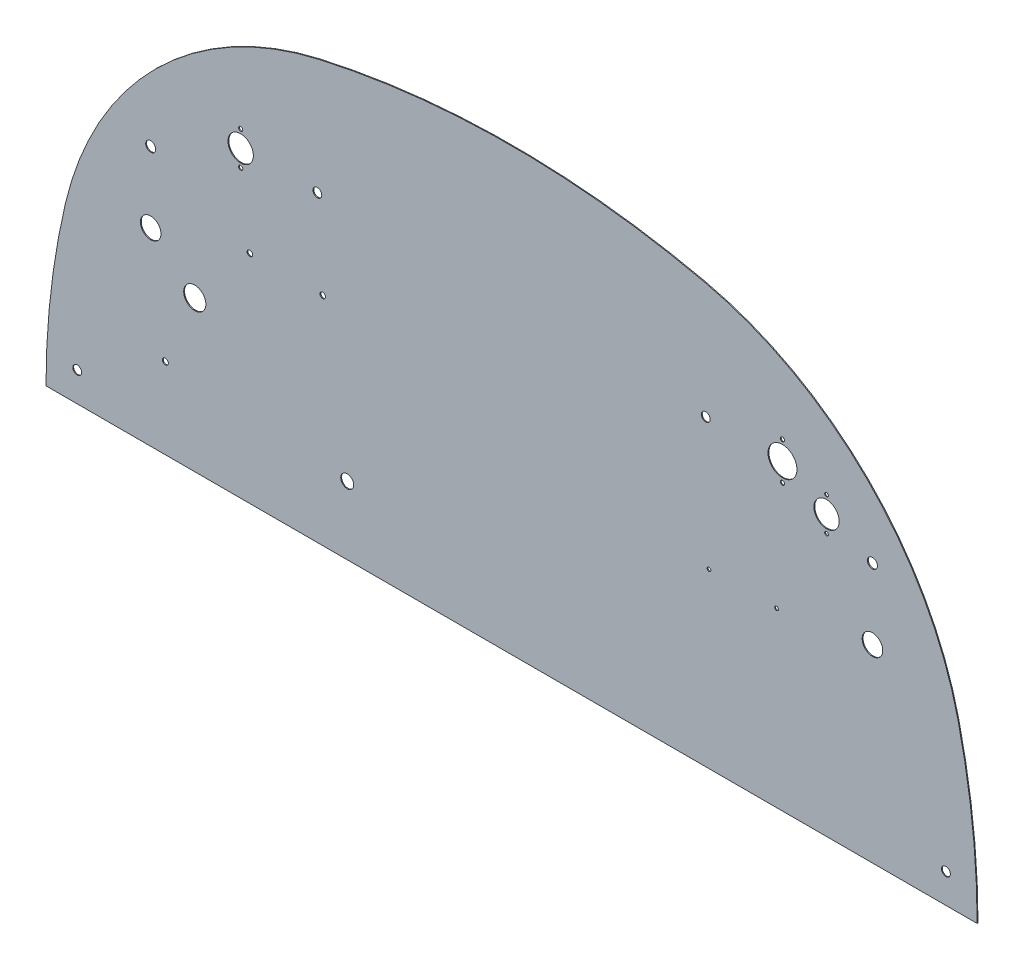
SolidWorks part; units mm, degrees
ref_plane "Front Plane" through (0, 0, 0) normal (0, 0, 1) x (1, 0, 0)
ref_plane "Top Plane" through (0, 0, 0) normal (0, 1, 0) x (1, 0, 0)
ref_plane "Right Plane" through (0, 0, 0) normal (1, 0, 0) x (0, 0, -1)
sketch "Base Sketch" plane through (0, 0, 0) normal (0, 0, 1) x (1, 0, 0)
  line L0 (0, 0) -> (750.8875, 0) construction
  line L1 (375.4437, 0) -> (375.4437, 236.5375) construction
  line L2 (543.3219, 236.5375) -> (207.5656, 236.5375) construction
  line L3 (-26.9875, -25.4) -> (777.875, -25.4)
  line L4 (375.4437, 0) -> (375.4437, -25.4) construction
  line L5 (375.4437, 236.5375) -> (375.4437, 355.6) construction
  line L6 (375.4437, 355.6) -> (-26.9875, 355.6) construction
  line L7 (-1.5875, -25.4) -> (375.4437, -25.4) construction
  line L8 (-1.5875, -25.4) -> (-1.5875, 152.4) construction
  line L9 (-1.5875, 152.4) -> (375.4437, 152.4) construction
  line L10 (375.4437, -25.4) -> (375.4437, 152.4) construction
  line L11 (23.8125, -25.4) -> (375.4437, -25.4) construction
  line L12 (23.8125, -25.4) -> (23.8125, 203.2) construction
  line L13 (23.8125, 203.2) -> (375.4437, 203.2) construction
  line L14 (375.4437, -25.4) -> (375.4437, 203.2) construction
  line L15 (49.2125, -25.4) -> (375.4437, -25.4) construction
  line L16 (49.2125, -25.4) -> (49.2125, 228.6) construction
  line L17 (49.2125, 228.6) -> (375.4437, 228.6) construction
  line L18 (375.4437, -25.4) -> (375.4437, 228.6) construction
  line L19 (74.6125, -25.4) -> (375.4437, -25.4) construction
  line L20 (74.6125, -25.4) -> (74.6125, 254) construction
  line L21 (74.6125, 254) -> (375.4437, 254) construction
  line L22 (375.4437, -25.4) -> (375.4437, 254) construction
  line L23 (100.0125, -25.4) -> (375.4437, -25.4) construction
  line L24 (100.0125, -25.4) -> (100.0125, 276.225) construction
  line L25 (100.0125, 276.225) -> (375.4437, 276.225) construction
  line L26 (375.4437, -25.4) -> (375.4437, 276.225) construction
  line L27 (125.4125, -25.4) -> (375.4437, -25.4) construction
  line L28 (125.4125, -25.4) -> (125.4125, 292.1) construction
  line L29 (125.4125, 292.1) -> (375.4437, 292.1) construction
  line L30 (375.4437, -25.4) -> (375.4437, 292.1) construction
  line L31 (150.8125, -25.4) -> (375.4437, -25.4) construction
  line L32 (150.8125, -25.4) -> (150.8125, 301.625) construction
  line L33 (150.8125, 301.625) -> (375.4437, 301.625) construction
  line L34 (375.4437, -25.4) -> (375.4437, 301.625) construction
  line L35 (176.2125, -25.4) -> (375.4437, -25.4) construction
  line L36 (176.2125, -25.4) -> (176.2125, 314.325) construction
  line L37 (176.2125, 314.325) -> (375.4437, 314.325) construction
  line L38 (375.4437, -25.4) -> (375.4437, 314.325) construction
  line L39 (201.6125, -25.4) -> (375.4437, -25.4) construction
  line L40 (201.6125, -25.4) -> (201.6125, 322.2625) construction
  line L41 (201.6125, 322.2625) -> (375.4437, 322.2625) construction
  line L42 (375.4437, -25.4) -> (375.4437, 322.2625) construction
  line L43 (227.0125, -25.4) -> (375.4437, -25.4) construction
  line L44 (227.0125, -25.4) -> (227.0125, 330.2) construction
  line L45 (227.0125, 330.2) -> (375.4437, 330.2) construction
  line L46 (375.4437, -25.4) -> (375.4437, 330.2) construction
  line L47 (252.4125, -25.4) -> (375.4437, -25.4) construction
  line L48 (252.4125, -25.4) -> (252.4125, 338.1375) construction
  line L49 (252.4125, 338.1375) -> (375.4437, 338.1375) construction
  line L50 (375.4437, -25.4) -> (375.4437, 338.1375) construction
  line L51 (277.8125, -25.4) -> (375.4437, -25.4) construction
  line L52 (277.8125, -25.4) -> (277.8125, 349.25) construction
  line L53 (277.8125, 349.25) -> (375.4437, 349.25) construction
  line L54 (375.4437, -25.4) -> (375.4437, 349.25) construction
  line L55 (-26.9875, -25.4) -> (-26.9875, 355.6) construction
  circle A0 centre (0, 0) radius 3.81
  circle A1 centre (750.8875, 0) radius 3.81
  circle A2 centre (207.5656, 236.5375) radius 3.81
  circle A3 centre (543.3219, 236.5375) radius 3.81
  arc A4 (-26.9875, -25.4) -> (777.875, -25.4) centre (375.4437, -47.434) cw construction
  arc A8 (-26.9875, -25.4) -> (-10.2771, 119.3168) centre (608.0125, -25.4) cw
  arc A9 (-10.2771, 119.3168) -> (208.9647, 336.9843) centre (273.2915, 52.9448) cw
  arc A10 (208.9647, 336.9843) -> (541.9228, 336.9843) centre (375.4437, -398.1152) cw
  arc A11 (761.1646, 119.3168) -> (541.9228, 336.9843) centre (477.596, 52.9448) ccw
  arc A12 (777.875, -25.4) -> (761.1646, 119.3168) centre (142.875, -25.4) ccw
  point P9 (375.4437, 236.5375)
  point P59 (0, 0)
  point P61 (0, 0)
  dimension "D1" = 7.62
  dimension "D2" = 750.8875
  dimension "D3" = 236.5375
  dimension "D4" = 335.7562
  dimension "D5" = 25.4
  dimension "D6" = 26.9875
  dimension "D8" = 25.4
  dimension "D9" = 177.8
  dimension "D10" = 50.8
  dimension "D11" = 228.6
  dimension "D12" = 76.2
  dimension "D13" = 254
  dimension "D14" = 101.6
  dimension "D15" = 279.4
  dimension "D16" = 127
  dimension "D17" = 301.625
  dimension "D18" = 152.4
  dimension "D19" = 317.5
  dimension "D20" = 177.8
  dimension "D21" = 327.025
  dimension "D22" = 203.2
  dimension "D23" = 339.725
  dimension "D24" = 228.6
  dimension "D25" = 347.6625
  dimension "D26" = 254
  dimension "D27" = 355.6
  dimension "D28" = 279.4
  dimension "D29" = 363.5375
  dimension "D30" = 304.8
  dimension "D31" = 374.65
extrude "Base w Mount Holes" add sketch "Base Sketch" along normal blind 0.7366
sketch "Throttle and Choke Cutout Sketch" plane through (0, 0, 0.7366) normal (0, 0, 1) x (1, 0, 0)
  line L0 (375.4438, -25.4) -> (375.4438, 355.6) construction
  line L2 (63.5, 199.0725) -> (63.5, 138.1125) construction
  line L3 (-26.9875, -25.4) -> (777.875, -25.4) construction
  line L4 (687.3875, 199.0725) -> (687.3875, 138.1125) construction
  circle A1 centre (63.5, 138.1125) radius 8.89
  circle A2 centre (63.5, 199.0725) radius 4.318
  arc A5 (541.9228, 336.9843) -> (208.9647, 336.9843) centre (375.4437, -398.1152) ccw construction
  circle A6 centre (687.3875, 199.0725) radius 4.318
  circle A7 centre (687.3875, 138.1125) radius 8.89
  point P11 (0, 0)
  dimension "D1" = 17.78
  dimension "D2" = 8.636
  dimension "D3" = 63.5
  dimension "D4" = 138.1125
  dimension "D5" = 199.0725
extrude "Throttle and Choke Cutouts" cut sketch "Throttle and Choke Cutout Sketch" against normal through all
sketch "Starter Relay Mount Sketch" plane through (0, 0, 0.7366) normal (0, 0, 1) x (1, 0, 0)
  line L0 (149.225, 161.925) -> (212.217, 161.925) construction
  circle A0 centre (149.225, 161.925) radius 2.3813
  circle A1 centre (212.217, 161.925) radius 2.3813
  dimension "D2" = 4.7625
  dimension "D1" = 62.992
  dimension "D3" = 149.225
  dimension "D4" = 161.925
extrude "Starter Relay Mount" cut sketch "Starter Relay Mount Sketch" against normal through all
sketch "Oil Pressure Sender Clamp Mount Sketch" plane through (0, 0, 0.7366) normal (0, 0, 1) x (1, 0, 0)
  circle A0 centre (76.2, 44.45) radius 2.54
  dimension "D1" = 5.08
  dimension "D2" = 76.2
  dimension "D3" = 44.45
extrude "Oil Pressure Sender Clamp Mount" cut sketch "Oil Pressure Sender Clamp Mount Sketch" against normal through all contours A0
sketch "Starter Power Cutout Sketch" plane through (0, 0, 0.7366) normal (0, 0, 1) x (1, 0, 0)
  circle A0 centre (233.3625, 33.3375) radius 5.588
  dimension "D1" = 11.176
  dimension "D2" = 233.3625
  dimension "D3" = 33.3375
extrude "Starter Power Cutout" cut sketch "Starter Power Cutout Sketch" against normal through all
sketch "Fuel Return Cutout Sketch" plane through (0, 0, 0.7366) normal (0, 0, 1) x (1, 0, 0)
  circle A0 centre (101.6, 104.775) radius 9.5758
  dimension "D3" = 19.1516
  dimension "D1" = 101.6
  dimension "D2" = 104.775
extrude "Fuel Return Cutout" cut sketch "Fuel Return Cutout Sketch" against normal through all
sketch "Brake Master Cyl Mount Sketch" plane through (0, 0, 0.7366) normal (0, 0, 1) x (1, 0, 0)
  line L0 (546.1, 123.825) -> (604.52, 123.825) construction
  circle A0 centre (546.1, 123.825) radius 1.6256
  circle A1 centre (604.52, 123.825) radius 1.6256
  dimension "D1" = 3.2512
  dimension "D2" = 546.1
  dimension "D3" = 123.825
  dimension "D4" = 58.42
extrude "Brake Master Cyl Mount" cut sketch "Brake Master Cyl Mount Sketch" against normal through all
sketch "Cutout - AS012 - Instrumentation Right Sketch" plane through (0, 0, 0.7366) normal (0, 0, 1) x (1, 0, 0)
  line L0 (141.2875, 221.9871) -> (141.2875, 236.5375) construction
  line L1 (141.2875, 236.5375) -> (141.2875, 251.0879) construction
  line L2 (207.5656, 236.5375) -> (543.3219, 236.5375) construction
  line L3 (141.2875, 236.5375) -> (207.5656, 236.5375) construction
  circle A0 centre (141.2875, 236.5375) radius 10.9499
  circle A1 centre (141.2875, 221.9871) radius 1.8034
  circle A2 centre (141.2875, 251.0879) radius 1.8034
  dimension "D1" = 21.8999
  dimension "D2" = 3.6068
  dimension "D3" = 29.1008
  dimension "D4" = 141.2875
extrude "Cutout - AS012 - Instrumentation Right" cut sketch "Cutout - AS012 - Instrumentation Right Sketch" against normal through all
sketch "Cutout - AS014 - Tach and CDI Enables Left Sketch" plane through (0, 0, 0.7366) normal (0, 0, 1) x (1, 0, 0)
  line L0 (609.6, 220.2878) -> (609.6, 236.5375) construction
  line L1 (609.6, 236.5375) -> (609.6, 252.7871) construction
  line L2 (609.6, 236.5375) -> (543.3219, 236.5375) construction
  circle A0 centre (609.6, 236.5375) radius 12.4968
  circle A1 centre (609.6, 252.7871) radius 1.8034
  circle A2 centre (609.6, 220.2878) radius 1.8034
  dimension "D2" = 3.6068
  dimension "D3" = 24.9936
  dimension "D1" = 32.4993
  dimension "D4" = 609.6
extrude "Cutout - AS014 - Tach and CDI Enables Left" cut sketch "Cutout - AS014 - Tach and CDI Enables Left Sketch" against normal through all
sketch "Cutout - AS012 - Instrumentation Left Sketch" plane through (0, 0, 0.7366) normal (0, 0, 1) x (1, 0, 0)
  line L0 (647.7, 201.3496) -> (647.7, 215.9) construction
  line L1 (647.7, 215.9) -> (647.7, 230.4504) construction
  circle A0 centre (647.7, 215.9) radius 10.9499
  circle A1 centre (647.7, 230.4504) radius 1.6002
  circle A2 centre (647.7, 201.3496) radius 1.6002
  dimension "D1" = 21.8999
  dimension "D2" = 3.2004
  dimension "D3" = 29.1008
  dimension "D4" = 647.7
  dimension "D5" = 215.9
extrude "Cutout - AS012 - Instrumentation Left" cut sketch "Cutout - AS012 - Instrumentation Left Sketch" against normal through all
